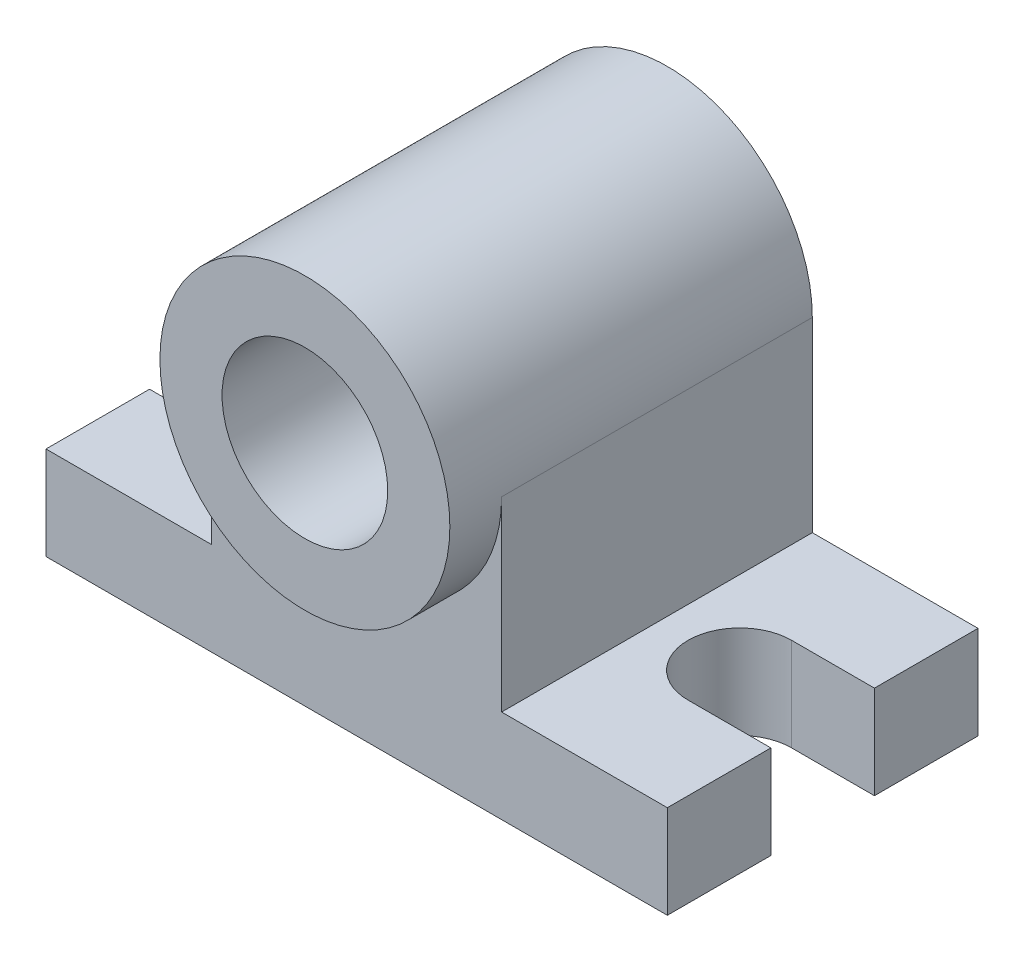
SolidWorks part; units mm, degrees
ref_plane "前视基准面" through (0, 0, 0) normal (0, 0, 1) x (1, 0, 0)
ref_plane "上视基准面" through (0, 0, 0) normal (0, 1, 0) x (1, 0, 0)
ref_plane "右视基准面" through (0, 0, 0) normal (1, 0, 0) x (0, 0, -1)
other "Configuration Table"
sketch "草图1" plane through (0, 0, 0) normal (0, 0, 1) x (1, 0, 0)
  line L0 (-33.8106, 0) -> (33.8106, 0) construction
  line L1 (0, -39.9471) -> (0, 39.9471) construction
  line L2 (14, -18) -> (30, -18)
  line L3 (-14, 0) -> (14, 0)
  line L4 (-14, 0) -> (-14, -18)
  line L6 (14, 0) -> (14, -18)
  line L7 (-30, -27) -> (30, -27)
  line L8 (-30, -27) -> (-30, -18)
  line L9 (-30, -18) -> (-14, -18)
  line L10 (30, -27) -> (30, -18)
  line L11 (-30, -27) -> (30, -18) construction
  line L12 (-30, -18) -> (30, -27) construction
  circle A0 centre (0, 0) radius 8
  circle A1 centre (0, 0) radius 14
  point P4 (0, 0)
  point P8 (0, 0)
  point P15 (0, -22.5)
  dimension "D1" = 28
  dimension "D2" = 16
  dimension "D3" = 27
  dimension "D4" = 9
  dimension "D5" = 60
extrude "凸台-拉伸1" add sketch "草图1" against normal blind 30 contours L3 A1 A0 | L3 A1 A0 | A1 L4 L9 L8 L7 L10 L2 L6 region at (0, -20.1823, 0) region at (0, -13.687, 0) region at (11, 0.313, 0)
extrude "凸台-拉伸2" add sketch "草图1<3>" along normal blind 5 contours L3 A1 A0 | L3 A1 A0 region at (0, -13.687, 0) region at (11, 0.313, 0)
sketch "草图1<3>" plane through (0, 0, 0) normal (0, 0, 1) x (1, 0, 0) same geometry as "草图1"
sketch "草图2" plane through (0, -18, 0) normal (0, 1, 0) x (1, 0, 0)
  line L0 (-30, 30) -> (30, 30) construction
  line L1 (30, 30) -> (30, 0) construction
  line L2 (0, 30) -> (0.0001, 30) construction
  line L3 (0, 30) -> (0, 0.0013) construction
  line L4 (28.3287, 15) -> (22, 15) construction
  line L5 (30, 10) -> (22, 10)
  line L6 (30, 20) -> (22, 20)
  line L7 (30, 30) -> (30, 0) construction
  line L8 (-28.3287, 15) -> (-22, 15) construction
  line L9 (-30, 20) -> (-22, 20)
  line L10 (-30, 10) -> (-22, 10)
  line L11 (-30, 20) -> (-30, 10)
  line L12 (-30, 30) -> (-30, 0) construction
  line L13 (30, 20) -> (30, 10)
  arc A1 (22, 20) -> (22, 10) centre (22, 15) ccw
  arc A2 (-22, 20) -> (-22, 10) centre (-22, 15) cw
  point P10 (30, 15)
  point P22 (-30, 15)
  dimension "D1" = 44
  dimension "D2" = 10
extrude "切除-拉伸1" cut sketch "草图2" against normal through all
